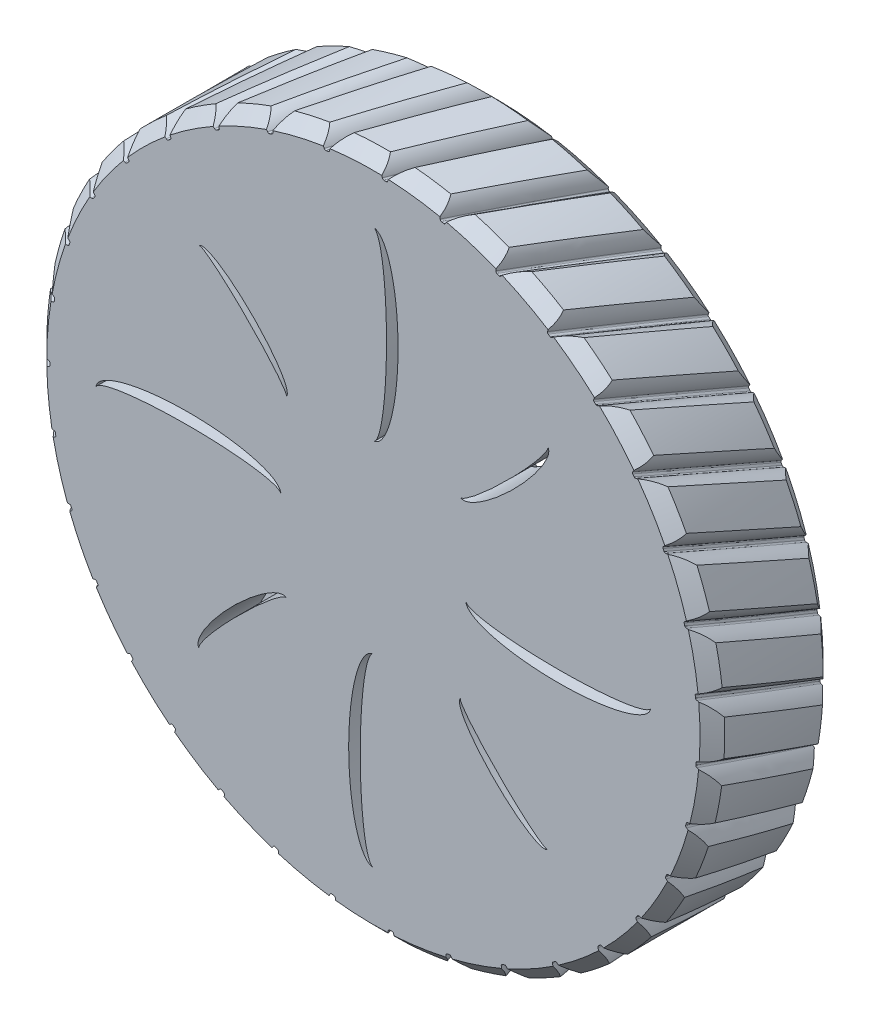
SolidWorks part; units mm, degrees
ref_plane "Front Plane" through (0, 0, 0) normal (0, 0, 1) x (1, 0, 0)
ref_plane "Top Plane" through (0, 0, 0) normal (0, 1, 0) x (1, 0, 0)
ref_plane "Right Plane" through (0, 0, 0) normal (1, 0, 0) x (0, 0, -1)
sketch "Sketch1" plane through (0, 0, 0) normal (0, 0, 1) x (1, 0, 0)
  line L0 (0, 0) -> (0, 2.8567) construction
  line L1 (-1.2298, 1.1) -> (1.2298, 1.1)
  circle A0 centre (0, 0) radius 22
  circle A1 centre (0, 0) radius 4
  arc A2 (-1.2298, 1.1) -> (1.2298, 1.1) centre (0, 0) ccw
  circle A3 centre (0, 0) radius 19
  dimension "D1" = 44
  dimension "D2" = 8
  dimension "D3" = 3.3
  dimension "D5" = 38
  dimension "D4" = 1.1
extrude "Boss-Extrude1" add sketch "Sketch1" against normal blind 4 contours A2 L1
extrude "Boss-Extrude2" add sketch "Sketch1<4>" against normal blind 8 contours A0 A3 | A1 A2 L1 region at (-21.3777, 0, 0) region at (-3.8869, 0, 0)
sketch "Sketch1<4>" plane through (0, 0, 0) normal (0, 0, 1) x (1, 0, 0) same geometry as "Sketch1"
extrude "Boss-Extrude3" add sketch "Sketch1<5>" against normal blind 4 contours A3 A1 region at (-18.4626, 0, 0)
sketch "Sketch1<5>" plane through (0, 0, 0) normal (0, 0, 1) x (1, 0, 0) same geometry as "Sketch1"
chamfer "Chamfer1" distance 0.8 angle 45 3 edges at (22, 0, 0) (4, 0, -8) (22, 0, -8)
sketch "Sketch4" plane through (0, 0, -8) normal (0, 0, -1) x (-1, 0, 0)
  circle A0 centre (0, 0) radius 22
  point P3 (0, 0)
  dimension "D1" = 44
curve "Helix/Spiral1" pitch 350 height 40 radius 22 centre (0, 0, -8) axis (0, 0, 1) start towards (0, 1, 0)
sketch "Sketch5" plane through (0, 0, -8) normal (0, 0, -1) x (-1, 0, 0)
  line L0 (0, 0) -> (0, 23.834) construction
  line L1 (-0.075, 21) -> (0.075, 21)
  arc A0 (0.8, 21.9854) -> (0, 22) centre (0, 0) ccw
  circle A1 centre (0, 0) radius 22 construction
  arc A2 (-0.8, 21.9854) -> (0, 22) centre (0, 0) cw
  arc A3 (-0.8, 21.9854) -> (-0.1739, 21.0854) centre (-2.0659, 20.4371) cw
  arc A4 (0.8, 21.9854) -> (0.1739, 21.0854) centre (2.0659, 20.4371) ccw
  arc A5 (-0.1739, 21.0854) -> (-0.075, 21) centre (-0.075, 21.1) ccw
  arc A6 (0.1739, 21.0854) -> (0.075, 21) centre (0.075, 21.1) cw
  point P5 (0, 21)
  point P14 (0.4001, 21.9964)
  point P15 (-0.4001, 21.9964)
  dimension "D1" = 0.8
  dimension "D3" = 2
  dimension "D4" = 0.1
  dimension "D6" = 0.9
  dimension "D2" = 0.15
  dimension "D5" = 1
sweep "Cut-Sweep1" cut profiles "Sketch5" path "Helix/Spiral1" align with end faces yes
pattern_circular "CirPattern1" count 35 over 360 about axis through (0, 0, -8) along (0, 0, 1) of "Cut-Sweep1"
sketch "Sketch6" plane through (0, 0, 0) normal (0, 0, 1) x (1, 0, 0)
  line L0 (-39.5277, 0) -> (39.5277, 0) construction
  line L1 (0, 24.8698) -> (0, -24.8698) construction
  line L2 (-18.3908, -18.3908) -> (18.3908, 18.3908) construction
  line L3 (22.3815, -22.3815) -> (-22.3815, 22.3815) construction
  circle A0 centre (0, 0) radius 4 construction
  ellipse E0 centre (0, 12) end of major axis (0, 18) minor radius 0.85 (0, 6) -> (0, 18) ccw
  ellipse E1 centre (0, 12) end of major axis (0, 6) minor radius 1.6 (0, 6) -> (0, 18) ccw
  ellipse E2 centre (12, 0) end of major axis (18, 0) minor radius 0.85 (6, 0) -> (18, 0) ccw
  ellipse E3 centre (12, 0) end of major axis (18, 0) minor radius 1.6 (6, 0) -> (18, 0) ccw
  ellipse E4 centre (0, -12) end of major axis (0, -18) minor radius 0.85 (0, -6) -> (0, -18) ccw
  ellipse E5 centre (0, -12) end of major axis (0, -18) minor radius 1.6 (0, -6) -> (0, -18) ccw
  ellipse E6 centre (-12, 0) end of major axis (-18, 0) minor radius 0.85 (-6, 0) -> (-18, 0) ccw
  ellipse E7 centre (-12, 0) end of major axis (-18, 0) minor radius 1.6 (-6, 0) -> (-18, 0) ccw
  ellipse E8 centre (-8.4853, 8.4853) end of major axis (-5.6569, 5.6569) minor radius 0.4 (-5.6569, 5.6569) -> (-11.3137, 11.3137) ccw
  ellipse E9 centre (-8.4853, 8.4853) end of major axis (-5.6569, 5.6569) minor radius 0.9 (-5.6569, 5.6569) -> (-11.3137, 11.3137) ccw
  ellipse E10 centre (8.4853, 8.4853) end of major axis (11.3137, 11.3137) minor radius 0.4 (5.6569, 5.6569) -> (11.3137, 11.3137) ccw
  ellipse E11 centre (8.4853, 8.4853) end of major axis (11.3137, 11.3137) minor radius 0.9 (5.6569, 5.6569) -> (11.3137, 11.3137) ccw
  ellipse E12 centre (8.4853, -8.4853) end of major axis (11.3137, -11.3137) minor radius 0.4 (5.6569, -5.6569) -> (11.3137, -11.3137) ccw
  ellipse E13 centre (8.4853, -8.4853) end of major axis (11.3137, -11.3137) minor radius 0.9 (5.6569, -5.6569) -> (11.3137, -11.3137) ccw
  ellipse E14 centre (-8.4853, -8.4853) end of major axis (-11.3137, -11.3137) minor radius 0.4 (-5.6569, -5.6569) -> (-11.3137, -11.3137) ccw
  ellipse E15 centre (-8.4853, -8.4853) end of major axis (-11.3137, -11.3137) minor radius 0.9 (-5.6569, -5.6569) -> (-11.3137, -11.3137) ccw
  point P4 (0, 0)
  point P8 (0, 0)
  point P56 (0, 0)
  point P59 (0, 0)
  dimension "D5" = 8
  dimension "D1" = 6
  dimension "D2" = 12
  dimension "D3" = 1.6
  dimension "D4" = 0.85
  dimension "D7" = 45
  dimension "D8" = 12
  dimension "D9" = 12
  dimension "D10" = 4
  dimension "D11" = 0.9
  dimension "D12" = 0.4
  dimension "D6" = 4
  dimension "D13" = 4
extrude "Cut-Extrude1" cut sketch "Sketch6" against normal blind 18
